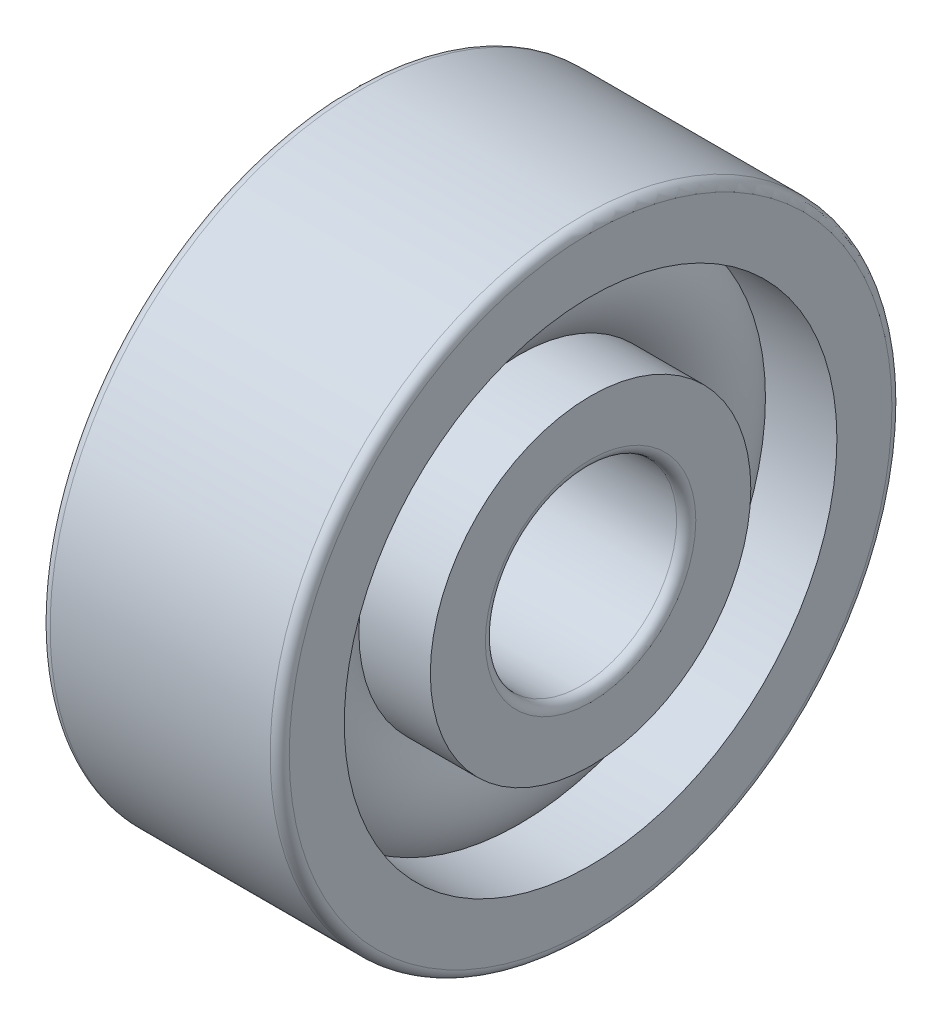
SolidWorks part; units mm, degrees
ref_plane "Plane1" through (0, 0, 0) normal (0, 0, 1) x (1, 0, 0)
ref_plane "Plane2" through (0, 0, 0) normal (0, 1, 0) x (1, 0, 0)
ref_plane "Plane3" through (0, 0, 0) normal (1, 0, 0) x (0, 0, -1)
other "Configuration Table"
sketch "Clipboard" plane through (0, 0, 0) normal (0, 0, 1) x (1, 0, 0)
  line L0 (-10, 0) -> (10, 0) construction
  line L1 (0, 0) -> (22.3471, -0.7804)
  line L2 (0, 0) -> (4.2474, 0.1483)
  line L3 (0, 0) -> (22.3471, -0.7804)
  line L4 (0, 0) -> (-22.3573, -0.3902)
  dimension "BallCLRad" = 4.25
sketch "CagSpiSke" plane through (0, 0, 0) normal (0, 0, 1) x (1, 0, 0)
  line L0 (0.135, 4.025) -> (0.135, 4.475)
  line L1 (0.135, 4.475) -> (-0.135, 4.475)
  line L2 (-0.135, 4.475) -> (-0.135, 4.025)
  line L3 (-0.135, 4.025) -> (0.135, 4.025)
  line L4 (-20.6375, 0) -> (20.6375, 0) construction
  line L5 (0, 0) -> (0, 23.7692) construction
  dimension "OD" = 8.95
  dimension "ID" = 8.05
revolve "CageSpine" add sketch "CagSpiSke" angle 0.001 about L4 reverse direction yes
ref_axis "Axis1" through (-50, 0, 0) along (1, 0, 0)
sketch "CagBalSke" plane through (0, 0, 0) normal (0, 0, 1) x (1, 0, 0)
  line L0 (-1.485, 4.25) -> (1.485, 4.25)
  line L1 (-1.905, 4.25) -> (1.905, 4.25) construction
  line L2 (-10, 0) -> (10, 0) construction
  line L3 (0, 0) -> (0, 24) construction
  arc A0 (1.485, 4.25) -> (-1.485, 4.25) centre (0, 4.25) cw
  dimension "BallCLRad" = 4.25
revolve "CageBall" [suppressed] add sketch "CagBalSke" angle 360 about L1 reverse direction yes
pattern_circular "CageBalls" [suppressed] count 2 every 180 about axis through (-50, 0, 0) along (1, 0, 0)
sketch "CagTrmODSke" plane through (0, 0, 0) normal (0, 0, 1) x (1, 0, 0)
  line L0 (1.486, 4.475) -> (1.486, 5.736)
  line L1 (1.486, 5.736) -> (-1.486, 5.736)
  line L2 (-1.486, 5.736) -> (-1.486, 4.475)
  line L3 (-1.486, 4.475) -> (1.486, 4.475)
  line L4 (-20.6375, 0) -> (20.6375, 0) construction
  line L5 (0, 0) -> (0, 25) construction
  dimension "Width" = 2.972
  dimension "ID" = 8.95
  dimension "OD" = 11.472
revolve "CageTrimOD" [suppressed] cut sketch "CagTrmODSke" angle 360 about L4 reverse direction yes
sketch "CagTrmIDSke" plane through (0, 0, 0) normal (0, 0, 1) x (1, 0, 0)
  line L0 (1.486, 2.766) -> (1.486, 4.025)
  line L1 (1.486, 4.025) -> (-1.486, 4.025)
  line L2 (-1.486, 4.025) -> (-1.486, 2.766)
  line L3 (-1.486, 2.766) -> (1.486, 2.766)
  line L4 (-20.6375, 0) -> (20.6375, 0) construction
  line L5 (0, 0) -> (0, 25) construction
  dimension "Width" = 2.972
  dimension "ID" = 5.532
  dimension "OD" = 8.05
revolve "CageTrimID" [suppressed] cut sketch "CagTrmIDSke" angle 360 about L4 reverse direction yes
sketch "BalSimSke" plane through (0, 0, 0) normal (0, 0, 1) x (1, 0, 0)
  line L0 (-10, 0) -> (10, 0) construction
  line L1 (-10, 4.25) -> (10, 4.25) construction
  line L2 (0, 0) -> (0, 23) construction
  circle A0 centre (0, 4.25) radius 1.35
  dimension "BallCLRad" = 4.25
  dimension "Ball_diameter" = 2.7
revolve "BallsSimplified" add sketch "BalSimSke" angle 360 about L0
sketch "BalDetSke" plane through (0, 0, 0) normal (0, 0, 1) x (1, 0, 0)
  line L0 (-1.35, 4.25) -> (1.35, 4.25)
  line L1 (-1.905, 4.25) -> (1.905, 4.25) construction
  line L2 (0, 0) -> (0, 25) construction
  arc A0 (1.35, 4.25) -> (-1.35, 4.25) centre (0, 4.25) cw
  dimension "BallCLRad" = 4.25
  dimension "Ball_diameter" = 2.7
revolve "BallDetailed" [suppressed] add sketch "BalDetSke" angle 360 about L1 reverse direction yes
sketch "InnRacSke" plane through (0, 0, 0) normal (0, 0, 1) x (1, 0, 0)
  line L0 (-0.9724, 3.35) -> (-2.5, 3.35)
  line L1 (-2.5, 3.35) -> (-2.5, 2.2)
  line L2 (-2.3, 2) -> (2.3, 2)
  line L3 (2.5, 2.2) -> (2.5, 3.35)
  line L4 (2.5, 3.35) -> (0.9724, 3.35)
  line L5 (-20.6375, 0) -> (20.6375, 0) construction
  line L6 (0, 0) -> (0, 30) construction
  arc A0 (-2.5, 2.2) -> (-2.3, 2) centre (-2.3, 2.2) ccw
  arc A1 (2.3, 2) -> (2.5, 2.2) centre (2.3, 2.2) ccw
  arc A2 (0.9724, 3.35) -> (-0.9724, 3.35) centre (0, 4.25) cw
  dimension "BallCLRad" = 4.25
  dimension "Fillet_radius" = 0.2
  dimension "Ball_diameter" = 2.65
  dimension "ID" = 4
  dimension "OD" = 6.7
  dimension "Width" = 5
revolve "InnerRace" add sketch "InnRacSke" angle 360 about L5 reverse direction yes
sketch "OutRacSke" plane through (0, 0, 0) normal (0, 0, 1) x (1, 0, 0)
  line L0 (-0.9724, 5.15) -> (-2.5, 5.15)
  line L1 (-2.5, 5.15) -> (-2.5, 6.3)
  line L2 (-2.3, 6.5) -> (2.3, 6.5)
  line L3 (2.5, 6.3) -> (2.5, 5.15)
  line L4 (2.5, 5.15) -> (0.9724, 5.15)
  line L5 (-20.6375, 0) -> (20.6375, 0) construction
  line L6 (0, 0) -> (0, 30) construction
  arc A0 (-2.5, 6.3) -> (-2.3, 6.5) centre (-2.3, 6.3) cw
  arc A1 (2.3, 6.5) -> (2.5, 6.3) centre (2.3, 6.3) cw
  arc A2 (0.9724, 5.15) -> (-0.9724, 5.15) centre (0, 4.25) ccw
  dimension "BallCLRad" = 4.25
  dimension "Fillet_radius" = 0.2
  dimension "Ball_diameter" = 2.65
  dimension "Width" = 5
revolve "OuterRace" add sketch "OutRacSke" angle 360 about L5 reverse direction yes
pattern_circular "BallsDetailed" [suppressed] count 2 every 180 about axis through (-50, 0, 0) along (1, 0, 0)
equation "\"BallCLRad@Clipboard\" = ( \"OD@OutRacSke\" + \"ID@InnRacSke\" ) / 4"
equation "\"BallCLRad@BalSimSke\" = \"BallCLRad@Clipboard\""
equation "\"BallCLRad@BalDetSke\" = \"BallCLRad@Clipboard\""
equation "\"BallCLRad@InnRacSke\" = \"BallCLRad@Clipboard\""
equation "\"BallCLRad@OutRacSke\" = \"BallCLRad@Clipboard\""
equation "\"Ball_diameter@InnRacSke\" = \"Ball_diameter@BalDetSke\" - 0.05"
equation "\"Ball_diameter@OutRacSke\" = \"Ball_diameter@BalDetSke\" - 0.05"
equation "\"Ball_diameter@BalSimSke\" = \"Ball_diameter@BalDetSke\""
equation "\"Width@OutRacSke\" = \"Width@InnRacSke\""
equation "\"Fillet_radius@OutRacSke\" = \"Fillet_radius@InnRacSke\""
equation "\"Max_count@Clipboard\" = int( 3.14159265 / atn(( \"Ball_diameter@BalDetSke\" / 2) / sqr( \"BallCLRad@Clipboard\"  *  \"BallCLRad@Clipboard\" - ( \"Ball_diameter@BalDetSke\" / 2) *  ( \"Ball_diameter@BalDetSke\" / 2))))"
equation "\"Max_count@Clipboard\" = ((sgn( \"Max_count@Clipboard\" - \"Count@Clipboard\" )-1)*( \"Max_count@Clipboard\" - \"Count@Clipboard\" ))/-2+ \"Count@Clipboard\""
equation "\"Count@BallsDetailed\" = int( \"Show_count@Clipboard\" ) "
equation "\"Count@BallsDetailed\" = ((sgn( \"Count@BallsDetailed\" - \"Max_count@Clipboard\" )-1)*( \"Count@BallsDetailed\" - \"Max_count@Clipboard\" ))/-2+ \"Max_count@Clipboard\""
equation "\"Count@BallsDetailed\" = ((sgn( \"Count@BallsDetailed\" - \"Min_count@Clipboard\" )+1)*( \"Count@BallsDetailed\" - \"Min_count@Clipboard\"))/2 +\"Min_count@Clipboard\""
equation "\"Angle@BallsDetailed\" = 360.0 / \"Max_count@Clipboard\""
equation "\"BallCLRad@CagBalSke\" = \"BallCLRad@Clipboard\""
equation "\"Count@CageBalls\" = \"Count@BallsDetailed\""
equation "\"Angle@CageBalls\" = \"Angle@BallsDetailed\""
equation "\"Angle@CageSpine\" =  \"Angle@CageBalls\" * ( \"Count@CageBalls\" -1 + int( \"Count@CageBalls\" / \"Max_count@Clipboard\" ) )  + 0.001 -  int( \"Count@CageBalls\" / \"Max_count@Clipboard\" ) * 0.001"
equation "\"Angle@CageSpine\" =  \"Angle@CageSpine\" * int( \"Min_count@Clipboard\" / 2) + int(1 / \"Min_count@Clipboard\")  * 0.001"
equation "\"CageWallOD@CagBalSke\" =  \"Ball_diameter@BalDetSke\" * 1.1"
equation "\"Thickness@CagSpiSke\" =  \"Ball_diameter@BalDetSke\" * 0.1"
equation "\"OD@CagTrmODSke\" = \"BallCLRad@Clipboard\" * 2 + \"CageWallOD@CagBalSke\" + 0.002"
equation "\"ID@CagTrmODSke\" = \"BallCLRad@Clipboard\" * 2 + \"Ball_diameter@BalDetSke\" / 6"
equation "\"OD@CagTrmIDSke\" = \"BallCLRad@Clipboard\" * 2 - \"Ball_diameter@BalDetSke\" / 6"
equation "\"ID@CagTrmIDSke\" = \"BallCLRad@Clipboard\" * 2 - \"CageWallOD@CagBalSke\" + 0.002"
equation "\"OD@CagSpiSke\" = \"ID@CagTrmODSke\""
equation "\"ID@CagSpiSke\" = \"OD@CagTrmIDSke\""
equation "\"Width@CagTrmODSke\" = \"CageWallOD@CagBalSke\" + 0.002"
equation "\"Width@CagTrmIDSke\" = \"CageWallOD@CagBalSke\" + 0.002"
